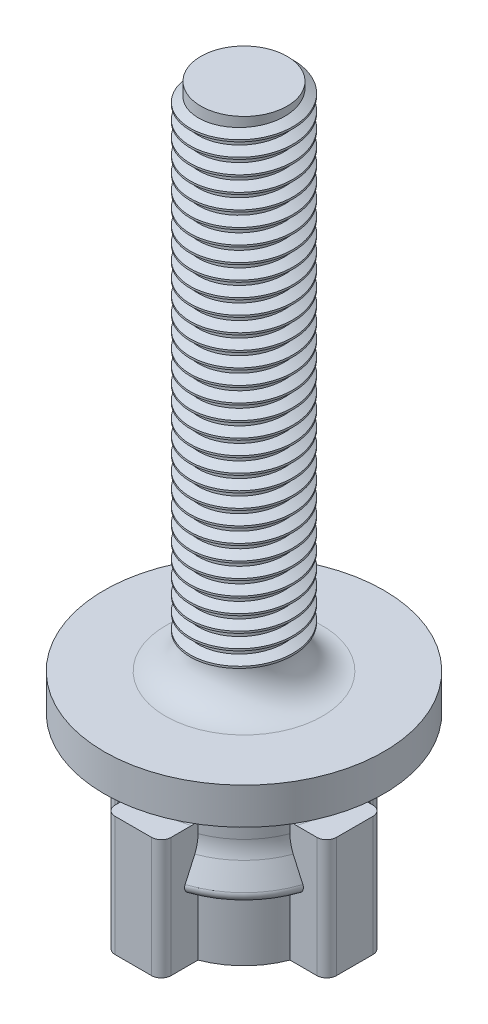
SolidWorks part; units mm, degrees
ref_plane "Alzado" through (0, 0, 0) normal (0, 0, 1) x (1, 0, 0)
ref_plane "Planta" through (0, 0, 0) normal (0, 1, 0) x (1, 0, 0)
ref_plane "Vista lateral" through (0, 0, 0) normal (1, 0, 0) x (0, 0, -1)
sketch "Croquis1" plane through (0, 0, 0) normal (0, 0, 1) x (1, 0, 0)
  line L0 (0, 0) -> (0, 10) construction
  line L1 (0, 10) -> (6.5, 10)
  line L2 (0, 0) -> (6.5, 0)
  line L3 (6.65, 0) -> (6.65, 4.8121) construction
  line L4 (6.8499, 5.007) -> (7, 5.007) construction
  line L5 (6.65, 9) -> (6.65, 10) construction
  line L6 (6.8889, 7.7374) -> (7.6384, 5.9716) construction
  line L7 (6.5, 10) -> (6.5, 9)
  line L8 (6.5, 4.8138) -> (6.5, 0)
  line L9 (6.8499, 5.157) -> (7, 5.157)
  line L10 (6.75, 7.6807) -> (7.5004, 5.9129)
  line L11 (0, 0) -> (0, 10)
  arc A0 (6.8499, 5.007) -> (6.65, 4.8121) centre (6.8499, 4.807) ccw construction
  arc A1 (7, 5.007) -> (7.6384, 5.9716) centre (7, 5.7006) ccw construction
  arc A2 (6.65, 9) -> (6.8889, 7.7374) centre (10.1063, 9) ccw construction
  arc A3 (6.8499, 5.157) -> (6.5, 4.8138) centre (6.8499, 4.807) ccw
  arc A4 (7, 5.157) -> (7.5004, 5.9129) centre (7, 5.7006) ccw
  arc A5 (6.5, 9) -> (6.75, 7.6807) centre (10.1063, 9) ccw
  dimension "D6" = 67
  dimension "D7" = 0.35
  dimension "D9" = 3.6063
  dimension "D11" = 0.15
  dimension "D1" = 10
  dimension "D2" = 6.5
  dimension "D3" = 0.15
  dimension "D4" = 4.8138
  dimension "D5" = 1
  dimension "D8" = 0.5
  dimension "D10" = 0.25
  dimension "D12" = 0.3499
  dimension "D13" = 0.35
  dimension "D15" = 0.0017
  dimension "D16" = 0.15
  dimension "D19" = 0.15
  dimension "D20" = 0.15
revolve "Revolución1" add sketch "Croquis1" angle 360 about L11
sketch "Croquis2" plane through (0, 10, 0) normal (0, 1, 0) x (1, 0, 0)
  line L0 (0, -7.5004) -> (0, 7.5004) construction
  line L1 (7.5004, 0) -> (-7.5004, 0) construction
  line L3 (-1.5, 9.3) -> (1.5, 9.3) construction
  line L4 (-2.5, 8.3) -> (-2.5, 6) construction
  line L5 (-2.5, 6) -> (2.5, 6) construction
  line L6 (2.5, 8.3) -> (2.5, 6) construction
  line L7 (-1.5, 9.1) -> (1.5, 9.1)
  line L11 (-2.3, 6.2) -> (2.3, 6.2) construction
  line L12 (2.3, 8.3) -> (2.3, 6.2) construction
  line L13 (2.3, 8.3) -> (2.3, 6)
  line L15 (-2.3, 8.3) -> (-2.3, 6.2) construction
  line L16 (-2.3, 8.3) -> (-2.3, 6)
  line L18 (-2.3, 6) -> (2.3, 6)
  line L31 (6, 2.3) -> (6, -2.3)
  line L32 (8.3, -2.3) -> (6, -2.3)
  line L33 (9.1, 1.5) -> (9.1, -1.5)
  line L34 (8.3, 2.3) -> (6, 2.3)
  line L35 (2.3, -6) -> (-2.3, -6)
  line L36 (-2.3, -8.3) -> (-2.3, -6)
  line L37 (1.5, -9.1) -> (-1.5, -9.1)
  line L38 (2.3, -8.3) -> (2.3, -6)
  line L39 (-6, -2.3) -> (-6, 2.3)
  line L40 (-8.3, 2.3) -> (-6, 2.3)
  line L41 (-9.1, -1.5) -> (-9.1, 1.5)
  line L42 (-8.3, -2.3) -> (-6, -2.3)
  arc A0 (1.5, 9.3) -> (2.5, 8.3) centre (1.5, 8.3) cw construction
  arc A1 (-1.5, 9.3) -> (-2.5, 8.3) centre (-1.5, 8.3) ccw construction
  circle A2 centre (0, 0) radius 6.5 construction
  arc A3 (1.5, 9.1) -> (2.3, 8.3) centre (1.5, 8.3) cw
  arc A4 (-1.5, 9.1) -> (-2.3, 8.3) centre (-1.5, 8.3) ccw
  circle A12 centre (0, 0) radius 7.5004 construction
  arc A13 (9.1, -1.5) -> (8.3, -2.3) centre (8.3, -1.5) cw
  arc A14 (9.1, 1.5) -> (8.3, 2.3) centre (8.3, 1.5) ccw
  arc A15 (-1.5, -9.1) -> (-2.3, -8.3) centre (-1.5, -8.3) cw
  arc A16 (1.5, -9.1) -> (2.3, -8.3) centre (1.5, -8.3) ccw
  arc A17 (-9.1, 1.5) -> (-8.3, 2.3) centre (-8.3, 1.5) cw
  arc A18 (-9.1, -1.5) -> (-8.3, -2.3) centre (-8.3, -1.5) ccw
  point P3 (0, 0)
  point P6 (0, 0)
  point P10 (0, 6)
  point P15 (-9.1, 0)
  point P16 (0, -9.1)
  point P39 (0, 0)
  point P56 (0, 0)
  dimension "D2" = 1
  dimension "D1" = 5
  dimension "D3" = 3.3
  dimension "D4" = 0.2
  dimension "D5" = 4
extrude "Saliente-Extruir1" add sketch "Croquis2" against normal up to surface (10 mm away) up to face at (0, 0, -6.5)
sketch "Croquis3" plane through (0, 10, 0) normal (0, 1, 0) x (1, 0, 0)
  line L12 (-2.3, -6.0795) -> (-2.3, -8.3)
  line L13 (2.3, 6.0795) -> (2.3, 8.3)
  line L14 (1.5, 9.1) -> (-1.5, 9.1)
  line L15 (-2.3, 8.3) -> (-2.3, 6.0795)
  line L16 (6.0795, -2.3) -> (8.3, -2.3)
  line L17 (9.1, -1.5) -> (9.1, 1.5)
  line L18 (8.3, 2.3) -> (6.0795, 2.3)
  line L19 (-2.3, -6.0795) -> (-2.3, -8.3)
  line L20 (-1.5, -9.1) -> (1.5, -9.1)
  line L21 (-1.5, -9.1) -> (1.5, -9.1)
  line L22 (2.3, -8.3) -> (2.3, -6.0795)
  line L23 (-6.0795, 2.3) -> (-8.3, 2.3)
  line L24 (-9.1, 1.5) -> (-9.1, -1.5)
  line L25 (-8.3, -2.3) -> (-6.0795, -2.3)
  line L26 (2.3, 6.0795) -> (2.3, 8.3)
  line L27 (1.5, 9.1) -> (-1.5, 9.1)
  line L28 (-2.3, 8.3) -> (-2.3, 6.0795)
  line L29 (6.0795, -2.3) -> (8.3, -2.3)
  line L30 (9.1, -1.5) -> (9.1, 1.5)
  line L31 (8.3, 2.3) -> (6.0795, 2.3)
  line L36 (-6.0795, 2.3) -> (-8.3, 2.3)
  line L37 (-9.1, 1.5) -> (-9.1, -1.5)
  line L38 (-8.3, -2.3) -> (-6.0795, -2.3)
  line L39 (2.3, -8.3) -> (2.3, -6.0795)
  arc A12 (-6.0795, -2.3) -> (-2.3, -6.0795) centre (0, 0) ccw
  arc A13 (2.3, 8.3) -> (1.5, 9.1) centre (1.5, 8.3) ccw
  arc A14 (-1.5, 9.1) -> (-2.3, 8.3) centre (-1.5, 8.3) ccw
  arc A15 (-2.3, 6.0795) -> (-6.0795, 2.3) centre (0, 0) ccw
  arc A16 (8.3, -2.3) -> (9.1, -1.5) centre (8.3, -1.5) ccw
  arc A17 (9.1, 1.5) -> (8.3, 2.3) centre (8.3, 1.5) ccw
  arc A18 (6.0795, 2.3) -> (2.3, 6.0795) centre (0, 0) ccw
  arc A19 (-2.3, -8.3) -> (-1.5, -9.1) centre (-1.5, -8.3) ccw
  arc A20 (-2.3, -8.3) -> (-1.5, -9.1) centre (-1.5, -8.3) ccw
  arc A21 (1.5, -9.1) -> (2.3, -8.3) centre (1.5, -8.3) ccw
  arc A22 (-8.3, 2.3) -> (-9.1, 1.5) centre (-8.3, 1.5) ccw
  arc A23 (-9.1, -1.5) -> (-8.3, -2.3) centre (-8.3, -1.5) ccw
  arc A24 (-6.0795, -2.3) -> (-2.3, -6.0795) centre (0, 0) ccw
  arc A25 (2.3, 8.3) -> (1.5, 9.1) centre (1.5, 8.3) ccw
  arc A26 (-1.5, 9.1) -> (-2.3, 8.3) centre (-1.5, 8.3) ccw
  arc A27 (-2.3, 6.0795) -> (-6.0795, 2.3) centre (0, 0) ccw
  arc A28 (8.3, -2.3) -> (9.1, -1.5) centre (8.3, -1.5) ccw
  arc A29 (9.1, 1.5) -> (8.3, 2.3) centre (8.3, 1.5) ccw
  arc A30 (6.0795, 2.3) -> (2.3, 6.0795) centre (0, 0) ccw
  arc A34 (-8.3, 2.3) -> (-9.1, 1.5) centre (-8.3, 1.5) ccw
  arc A35 (-9.1, -1.5) -> (-8.3, -2.3) centre (-8.3, -1.5) ccw
  arc A36 (1.5, -9.1) -> (2.3, -8.3) centre (1.5, -8.3) ccw
  arc A37 (2.3, -6.0795) -> (6.0795, -2.3) centre (0, 0) ccw
  arc A38 (2.3, -6.0795) -> (6.0795, -2.3) centre (0, 0) ccw
  dimension "D1" = 0
extrude "Cortar-Extruir1" cut sketch "Croquis3" against normal blind 0.15
sketch "Croquis5" plane through (0, 9.85, 0) normal (0, 1, 0) x (1, 0, 0)
  circle A1 centre (0, 0) radius 6
  dimension "D1" = 12
extrude "Saliente-Extruir2" add sketch "Croquis5" along normal blind 3.55
sketch "Croquis6" plane through (0, 13.4, 0) normal (0, 1, 0) x (1, 0, 0)
  circle A0 centre (0, 0) radius 11.5
  dimension "D1" = 23
extrude "Saliente-Extruir3" add sketch "Croquis6" along normal blind 3
sketch "Croquis8" plane through (0, 16.4, 0) normal (0, 1, 0) x (1, 0, 0)
  circle A0 centre (0, 0) radius 3.55
  dimension "D1" = 7.1
extrude "Saliente-Extruir4" add sketch "Croquis8" along normal blind 42
fillet "Redondeo5" radius 1 2 edges at (0, 9.85, 6) (0, 13.4, 6)
thread "Rosca1" pitch 1.25 profile "Perfil de rosca1" start angle 0, offset 0, length 39, pitch 1.25, diameter 7.1
ref_plane "Plano1" through (-3.55, 58.4, 0) normal (0, 0, 1) x (-1, 0, 0)
sketch "Perfil de rosca1" plane through (-3.55, 58.4, 0) normal (0, 0, 1) x (-1, 0, 0)
  line L0 (0, 0) -> (0, 1.25) construction
  line L1 (0, 0) -> (0.6766, 0.3906)
  line L2 (0.6766, 0.3906) -> (0.6766, 0.5469)
  line L3 (0.6766, 0.5469) -> (0, 0.9375)
  line L4 (0.6766, 0.4687) -> (0, 0.4687) construction
  line L11 (0, 0) -> (0, 0.9375)
  point P2 (0, 0)
  dimension "Pitch" = 1.25
  dimension "Profile_Angle" = 60
  dimension "Profile_Land" = 0.1562
  dimension "Profile_Height" = 0.6766
sketch3d "Croquis3D1"
  spline S0 degree 2 poles (-4.2266, 57.8531, 0) (-4.2266, 57.775, -1.7507) (-2.9886, 57.6969, -2.9886) (-1.7507, 57.6188, -4.2266) (0, 57.5406, -4.2266) (1.7507, 57.4625, -4.2266) (2.9886, 57.3844, -2.9886) (4.2266, 57.3063, -1.7507) (4.2266, 57.2281, 0) (4.2266, 57.15, 1.7507) (2.9886, 57.0719, 2.9886) (1.7507, 56.9938, 4.2266) (0, 56.9156, 4.2266) (-1.7507, 56.8375, 4.2266) (-2.9886, 56.7594, 2.9886) (-4.2266, 56.6813, 1.7507) (-4.2266, 56.6031, 0) (-4.2266, 56.525, -1.7507) (-2.9886, 56.4469, -2.9886) (-1.7507, 56.3688, -4.2266) (0, 56.2906, -4.2266) (1.7507, 56.2125, -4.2266) (2.9886, 56.1344, -2.9886) (4.2266, 56.0563, -1.7507) (4.2266, 55.9781, 0) (4.2266, 55.9, 1.7507) (2.9886, 55.8219, 2.9886) (1.7507, 55.7438, 4.2266) (0, 55.6656, 4.2266) (-1.7507, 55.5875, 4.2266) (-2.9886, 55.5094, 2.9886) (-4.2266, 55.4313, 1.7507) (-4.2266, 55.3531, 0) (-4.2266, 55.275, -1.7507) (-2.9886, 55.1969, -2.9886) (-1.7507, 55.1188, -4.2266) (0, 55.0406, -4.2266) (1.7507, 54.9625, -4.2266) (2.9886, 54.8844, -2.9886) (4.2266, 54.8063, -1.7507) (4.2266, 54.7281, 0) (4.2266, 54.65, 1.7507) (2.9886, 54.5719, 2.9886) (1.7507, 54.4938, 4.2266) (0, 54.4156, 4.2266) (-1.7507, 54.3375, 4.2266) (-2.9886, 54.2594, 2.9886) (-4.2266, 54.1813, 1.7507) (-4.2266, 54.1031, 0) (-4.2266, 54.025, -1.7507) (-2.9886, 53.9469, -2.9886) (-1.7507, 53.8688, -4.2266) (0, 53.7906, -4.2266) (1.7507, 53.7125, -4.2266) (2.9886, 53.6344, -2.9886) (4.2266, 53.5563, -1.7507) (4.2266, 53.4781, 0) (4.2266, 53.4, 1.7507) (2.9886, 53.3219, 2.9886) (1.7507, 53.2438, 4.2266) (0, 53.1656, 4.2266) (-1.7507, 53.0875, 4.2266) (-2.9886, 53.0094, 2.9886) (-4.2266, 52.9313, 1.7507) (-4.2266, 52.8531, 0) (-4.2266, 52.775, -1.7507) (-2.9886, 52.6969, -2.9886) (-1.7507, 52.6188, -4.2266) (0, 52.5406, -4.2266) (1.7507, 52.4625, -4.2266) (2.9886, 52.3844, -2.9886) (4.2266, 52.3063, -1.7507) (4.2266, 52.2281, 0) (4.2266, 52.15, 1.7507) (2.9886, 52.0719, 2.9886) (1.7507, 51.9938, 4.2266) (0, 51.9156, 4.2266) (-1.7507, 51.8375, 4.2266) (-2.9886, 51.7594, 2.9886) (-4.2266, 51.6813, 1.7507) (-4.2266, 51.6031, 0) (-4.2266, 51.525, -1.7507) (-2.9886, 51.4469, -2.9886) (-1.7507, 51.3688, -4.2266) (0, 51.2906, -4.2266) (1.7507, 51.2125, -4.2266) (2.9886, 51.1344, -2.9886) (4.2266, 51.0563, -1.7507) (4.2266, 50.9781, 0) (4.2266, 50.9, 1.7507) (2.9886, 50.8219, 2.9886) (1.7507, 50.7438, 4.2266) (0, 50.6656, 4.2266) (-1.7507, 50.5875, 4.2266) (-2.9886, 50.5094, 2.9886) (-4.2266, 50.4313, 1.7507) (-4.2266, 50.3531, 0) (-4.2266, 50.275, -1.7507) (-2.9886, 50.1969, -2.9886) (-1.7507, 50.1188, -4.2266) (0, 50.0406, -4.2266) (1.7507, 49.9625, -4.2266) (2.9886, 49.8844, -2.9886) (4.2266, 49.8063, -1.7507) (4.2266, 49.7281, 0) (4.2266, 49.65, 1.7507) (2.9886, 49.5719, 2.9886) (1.7507, 49.4938, 4.2266) (0, 49.4156, 4.2266) (-1.7507, 49.3375, 4.2266) (-2.9886, 49.2594, 2.9886) (-4.2266, 49.1813, 1.7507) (-4.2266, 49.1031, 0) (-4.2266, 49.025, -1.7507) (-2.9886, 48.9469, -2.9886) (-1.7507, 48.8688, -4.2266) (0, 48.7906, -4.2266) (1.7507, 48.7125, -4.2266) (2.9886, 48.6344, -2.9886) (4.2266, 48.5563, -1.7507) (4.2266, 48.4781, 0) (4.2266, 48.4, 1.7507) (2.9886, 48.3219, 2.9886) (1.7507, 48.2438, 4.2266) (0, 48.1656, 4.2266) (-1.7507, 48.0875, 4.2266) (-2.9886, 48.0094, 2.9886) (-4.2266, 47.9313, 1.7507) (-4.2266, 47.8531, 0) (-4.2266, 47.775, -1.7507) (-2.9886, 47.6969, -2.9886) (-1.7507, 47.6188, -4.2266) (0, 47.5406, -4.2266) (1.7507, 47.4625, -4.2266) (2.9886, 47.3844, -2.9886) (4.2266, 47.3063, -1.7507) (4.2266, 47.2281, 0) (4.2266, 47.15, 1.7507) (2.9886, 47.0719, 2.9886) (1.7507, 46.9938, 4.2266) (0, 46.9156, 4.2266) (-1.7507, 46.8375, 4.2266) (-2.9886, 46.7594, 2.9886) (-4.2266, 46.6813, 1.7507) (-4.2266, 46.6031, 0) (-4.2266, 46.525, -1.7507) (-2.9886, 46.4469, -2.9886) (-1.7507, 46.3688, -4.2266) (0, 46.2906, -4.2266) (1.7507, 46.2125, -4.2266) (2.9886, 46.1344, -2.9886) (4.2266, 46.0563, -1.7507) (4.2266, 45.9781, 0) (4.2266, 45.9, 1.7507) (2.9886, 45.8219, 2.9886) (1.7507, 45.7438, 4.2266) (0, 45.6656, 4.2266) (-1.7507, 45.5875, 4.2266) (-2.9886, 45.5094, 2.9886) (-4.2266, 45.4313, 1.7507) (-4.2266, 45.3531, 0) (-4.2266, 45.275, -1.7507) (-2.9886, 45.1969, -2.9886) (-1.7507, 45.1188, -4.2266) (0, 45.0406, -4.2266) (1.7507, 44.9625, -4.2266) (2.9886, 44.8844, -2.9886) (4.2266, 44.8063, -1.7507) (4.2266, 44.7281, 0) (4.2266, 44.65, 1.7507) (2.9886, 44.5719, 2.9886) (1.7507, 44.4938, 4.2266) (0, 44.4156, 4.2266) (-1.7507, 44.3375, 4.2266) (-2.9886, 44.2594, 2.9886) (-4.2266, 44.1813, 1.7507) (-4.2266, 44.1031, 0) (-4.2266, 44.025, -1.7507) (-2.9886, 43.9469, -2.9886) (-1.7507, 43.8688, -4.2266) (0, 43.7906, -4.2266) (1.7507, 43.7125, -4.2266) (2.9886, 43.6344, -2.9886) (4.2266, 43.5563, -1.7507) (4.2266, 43.4781, 0) (4.2266, 43.4, 1.7507) (2.9886, 43.3219, 2.9886) (1.7507, 43.2438, 4.2266) (0, 43.1656, 4.2266) (-1.7507, 43.0875, 4.2266) (-2.9886, 43.0094, 2.9886) (-4.2266, 42.9313, 1.7507) (-4.2266, 42.8531, 0) (-4.2266, 42.775, -1.7507) (-2.9886, 42.6969, -2.9886) (-1.7507, 42.6188, -4.2266) (0, 42.5406, -4.2266) (1.7507, 42.4625, -4.2266) (2.9886, 42.3844, -2.9886) (4.2266, 42.3063, -1.7507) (4.2266, 42.2281, 0) (4.2266, 42.15, 1.7507) (2.9886, 42.0719, 2.9886) (1.7507, 41.9938, 4.2266) (0, 41.9156, 4.2266) (-1.7507, 41.8375, 4.2266) (-2.9886, 41.7594, 2.9886) (-4.2266, 41.6813, 1.7507) (-4.2266, 41.6031, 0) (-4.2266, 41.525, -1.7507) (-2.9886, 41.4469, -2.9886) (-1.7507, 41.3688, -4.2266) (0, 41.2906, -4.2266) (1.7507, 41.2125, -4.2266) (2.9886, 41.1344, -2.9886) (4.2266, 41.0563, -1.7507) (4.2266, 40.9781, 0) (4.2266, 40.9, 1.7507) (2.9886, 40.8219, 2.9886) (1.7507, 40.7438, 4.2266) (0, 40.6656, 4.2266) (-1.7507, 40.5875, 4.2266) (-2.9886, 40.5094, 2.9886) (-4.2266, 40.4313, 1.7507) (-4.2266, 40.3531, 0) (-4.2266, 40.275, -1.7507) (-2.9886, 40.1969, -2.9886) (-1.7507, 40.1188, -4.2266) (0, 40.0406, -4.2266) (1.7507, 39.9625, -4.2266) (2.9886, 39.8844, -2.9886) (4.2266, 39.8063, -1.7507) (4.2266, 39.7281, 0) (4.2266, 39.65, 1.7507) (2.9886, 39.5719, 2.9886) (1.7507, 39.4938, 4.2266) (0, 39.4156, 4.2266) (-1.7507, 39.3375, 4.2266) (-2.9886, 39.2594, 2.9886) (-4.2266, 39.1813, 1.7507) (-4.2266, 39.1031, 0) (-4.2266, 39.025, -1.7507) (-2.9886, 38.9469, -2.9886) (-1.7507, 38.8688, -4.2266) (0, 38.7906, -4.2266) (1.7507, 38.7125, -4.2266) (2.9886, 38.6344, -2.9886) (4.2266, 38.5563, -1.7507) (4.2266, 38.4781, 0) (4.2266, 38.4, 1.7507) (2.9886, 38.3219, 2.9886) (1.7507, 38.2438, 4.2266) (0, 38.1656, 4.2266) (-1.7507, 38.0875, 4.2266) (-2.9886, 38.0094, 2.9886) (-4.2266, 37.9313, 1.7507) (-4.2266, 37.8531, 0) (-4.2266, 37.775, -1.7507) (-2.9886, 37.6969, -2.9886) (-1.7507, 37.6188, -4.2266) (0, 37.5406, -4.2266) (1.7507, 37.4625, -4.2266) (2.9886, 37.3844, -2.9886) (4.2266, 37.3063, -1.7507) (4.2266, 37.2281, 0) (4.2266, 37.15, 1.7507) (2.9886, 37.0719, 2.9886) (1.7507, 36.9938, 4.2266) (0, 36.9156, 4.2266) (-1.7507, 36.8375, 4.2266) (-2.9886, 36.7594, 2.9886) (-4.2266, 36.6813, 1.7507) (-4.2266, 36.6031, 0) (-4.2266, 36.525, -1.7507) (-2.9886, 36.4469, -2.9886) (-1.7507, 36.3688, -4.2266) (0, 36.2906, -4.2266) (1.7507, 36.2125, -4.2266) (2.9886, 36.1344, -2.9886) (4.2266, 36.0563, -1.7507) (4.2266, 35.9781, 0) (4.2266, 35.9, 1.7507) (2.9886, 35.8219, 2.9886) (1.7507, 35.7438, 4.2266) (0, 35.6656, 4.2266) (-1.7507, 35.5875, 4.2266) (-2.9886, 35.5094, 2.9886) (-4.2266, 35.4313, 1.7507) (-4.2266, 35.3531, 0) (-4.2266, 35.275, -1.7507) (-2.9886, 35.1969, -2.9886) (-1.7507, 35.1188, -4.2266) (0, 35.0406, -4.2266) (1.7507, 34.9625, -4.2266) (2.9886, 34.8844, -2.9886) (4.2266, 34.8063, -1.7507) (4.2266, 34.7281, 0) (4.2266, 34.65, 1.7507) (2.9886, 34.5719, 2.9886) (1.7507, 34.4938, 4.2266) (0, 34.4156, 4.2266) (-1.7507, 34.3375, 4.2266) (-2.9886, 34.2594, 2.9886) (-4.2266, 34.1813, 1.7507) (-4.2266, 34.1031, 0) (-4.2266, 34.025, -1.7507) (-2.9886, 33.9469, -2.9886) (-1.7507, 33.8688, -4.2266) (0, 33.7906, -4.2266) (1.7507, 33.7125, -4.2266) (2.9886, 33.6344, -2.9886) (4.2266, 33.5563, -1.7507) (4.2266, 33.4781, 0) (4.2266, 33.4, 1.7507) (2.9886, 33.3219, 2.9886) (1.7507, 33.2438, 4.2266) (0, 33.1656, 4.2266) (-1.7507, 33.0875, 4.2266) (-2.9886, 33.0094, 2.9886) (-4.2266, 32.9313, 1.7507) (-4.2266, 32.8531, 0) (-4.2266, 32.775, -1.7507) (-2.9886, 32.6969, -2.9886) (-1.7507, 32.6188, -4.2266) (0, 32.5406, -4.2266) (1.7507, 32.4625, -4.2266) (2.9886, 32.3844, -2.9886) (4.2266, 32.3063, -1.7507) (4.2266, 32.2281, 0) (4.2266, 32.15, 1.7507) (2.9886, 32.0719, 2.9886) (1.7507, 31.9938, 4.2266) (0, 31.9156, 4.2266) (-1.7507, 31.8375, 4.2266) (-2.9886, 31.7594, 2.9886) (-4.2266, 31.6813, 1.7507) (-4.2266, 31.6031, 0) (-4.2266, 31.525, -1.7507) (-2.9886, 31.4469, -2.9886) (-1.7507, 31.3688, -4.2266) (0, 31.2906, -4.2266) (1.7507, 31.2125, -4.2266) (2.9886, 31.1344, -2.9886) (4.2266, 31.0563, -1.7507) (4.2266, 30.9781, 0) (4.2266, 30.9, 1.7507) (2.9886, 30.8219, 2.9886) (1.7507, 30.7438, 4.2266) (0, 30.6656, 4.2266) (-1.7507, 30.5875, 4.2266) (-2.9886, 30.5094, 2.9886) (-4.2266, 30.4313, 1.7507) (-4.2266, 30.3531, 0) (-4.2266, 30.275, -1.7507) (-2.9886, 30.1969, -2.9886) (-1.7507, 30.1188, -4.2266) (0, 30.0406, -4.2266) (1.7507, 29.9625, -4.2266) (2.9886, 29.8844, -2.9886) (4.2266, 29.8063, -1.7507) (4.2266, 29.7281, 0) (4.2266, 29.65, 1.7507) (2.9886, 29.5719, 2.9886) (1.7507, 29.4938, 4.2266) (0, 29.4156, 4.2266) (-1.7507, 29.3375, 4.2266) (-2.9886, 29.2594, 2.9886) (-4.2266, 29.1813, 1.7507) (-4.2266, 29.1031, 0) (-4.2266, 29.025, -1.7507) (-2.9886, 28.9469, -2.9886) (-1.7507, 28.8688, -4.2266) (0, 28.7906, -4.2266) (1.7507, 28.7125, -4.2266) (2.9886, 28.6344, -2.9886) (4.2266, 28.5563, -1.7507) (4.2266, 28.4781, 0) (4.2266, 28.4, 1.7507) (2.9886, 28.3219, 2.9886) (1.7507, 28.2438, 4.2266) (0, 28.1656, 4.2266) (-1.7507, 28.0875, 4.2266) (-2.9886, 28.0094, 2.9886) (-4.2266, 27.9313, 1.7507) (-4.2266, 27.8531, 0) (-4.2266, 27.775, -1.7507) (-2.9886, 27.6969, -2.9886) (-1.7507, 27.6188, -4.2266) (0, 27.5406, -4.2266) (1.7507, 27.4625, -4.2266) (2.9886, 27.3844, -2.9886) (4.2266, 27.3063, -1.7507) (4.2266, 27.2281, 0) (4.2266, 27.15, 1.7507) (2.9886, 27.0719, 2.9886) (1.7507, 26.9938, 4.2266) (0, 26.9156, 4.2266) (-1.7507, 26.8375, 4.2266) (-2.9886, 26.7594, 2.9886) (-4.2266, 26.6813, 1.7507) (-4.2266, 26.6031, 0) (-4.2266, 26.525, -1.7507) (-2.9886, 26.4469, -2.9886) (-1.7507, 26.3688, -4.2266) (0, 26.2906, -4.2266) (1.7507, 26.2125, -4.2266) (2.9886, 26.1344, -2.9886) (4.2266, 26.0563, -1.7507) (4.2266, 25.9781, 0) (4.2266, 25.9, 1.7507) (2.9886, 25.8219, 2.9886) (1.7507, 25.7438, 4.2266) (0, 25.6656, 4.2266) (-1.7507, 25.5875, 4.2266) (-2.9886, 25.5094, 2.9886) (-4.2266, 25.4313, 1.7507) (-4.2266, 25.3531, 0) (-4.2266, 25.275, -1.7507) (-2.9886, 25.1969, -2.9886) (-1.7507, 25.1188, -4.2266) (0, 25.0406, -4.2266) (1.7507, 24.9625, -4.2266) (2.9886, 24.8844, -2.9886) (4.2266, 24.8063, -1.7507) (4.2266, 24.7281, 0) (4.2266, 24.65, 1.7507) (2.9886, 24.5719, 2.9886) (1.7507, 24.4938, 4.2266) (0, 24.4156, 4.2266) (-1.7507, 24.3375, 4.2266) (-2.9886, 24.2594, 2.9886) (-4.2266, 24.1813, 1.7507) (-4.2266, 24.1031, 0) (-4.2266, 24.025, -1.7507) (-2.9886, 23.9469, -2.9886) (-1.7507, 23.8688, -4.2266) (0, 23.7906, -4.2266) (1.7507, 23.7125, -4.2266) (2.9886, 23.6344, -2.9886) (4.2266, 23.5563, -1.7507) (4.2266, 23.4781, 0) (4.2266, 23.4, 1.7507) (2.9886, 23.3219, 2.9886) (1.7507, 23.2438, 4.2266) (0, 23.1656, 4.2266) (-1.7507, 23.0875, 4.2266) (-2.9886, 23.0094, 2.9886) (-4.2266, 22.9313, 1.7507) (-4.2266, 22.8531, 0) (-4.2266, 22.775, -1.7507) (-2.9886, 22.6969, -2.9886) (-1.7507, 22.6188, -4.2266) (0, 22.5406, -4.2266) (1.7507, 22.4625, -4.2266) (2.9886, 22.3844, -2.9886) (4.2266, 22.3063, -1.7507) (4.2266, 22.2281, 0) (4.2266, 22.15, 1.7507) (2.9886, 22.0719, 2.9886) (1.7507, 21.9938, 4.2266) (0, 21.9156, 4.2266) (-1.7507, 21.8375, 4.2266) (-2.9886, 21.7594, 2.9886) (-4.2266, 21.6813, 1.7507) (-4.2266, 21.6031, 0) (-4.2266, 21.525, -1.7507) (-2.9886, 21.4469, -2.9886) (-1.7507, 21.3688, -4.2266) (0, 21.2906, -4.2266) (1.7507, 21.2125, -4.2266) (2.9886, 21.1344, -2.9886) (4.2266, 21.0563, -1.7507) (4.2266, 20.9781, 0) (4.2266, 20.9, 1.7507) (2.9886, 20.8219, 2.9886) (1.7507, 20.7438, 4.2266) (0, 20.6656, 4.2266) (-1.7507, 20.5875, 4.2266) (-2.9886, 20.5094, 2.9886) (-4.2266, 20.4313, 1.7507) (-4.2266, 20.3531, 0) (-4.2266, 20.275, -1.7507) (-2.9886, 20.1969, -2.9886) (-1.7507, 20.1188, -4.2266) (0, 20.0406, -4.2266) (1.7507, 19.9625, -4.2266) (2.9886, 19.8844, -2.9886) (4.2266, 19.8063, -1.7507) (4.2266, 19.7281, 0) (4.2266, 19.65, 1.7507) (2.9886, 19.5719, 2.9886) (1.7507, 19.4938, 4.2266) (0, 19.4156, 4.2266) (-1.7507, 19.3375, 4.2266) (-2.9886, 19.2594, 2.9886) (-4.2266, 19.1813, 1.7507) (-4.2266, 19.1031, 0) (-4.2266, 19.025, -1.7507) (-2.9886, 18.9469, -2.9886) (-2.2711, 18.9016, -3.7061) (-1.3061, 18.8527, -4.0197) knots 0 0 0 0.003906 0.003906 0.007812 0.007812 0.011719 0.011719 0.015625 0.015625 0.019531 0.019531 0.023438 0.023438 0.027344 0.027344 0.03125 0.03125 0.035156 0.035156 0.039062 0.039062 0.042969 0.042969 0.046875 0.046875 0.050781 0.050781 0.054688 0.054688 0.058594 0.058594 0.0625 0.0625 0.066406 0.066406 0.070312 0.070312 0.074219 0.074219 0.078125 0.078125 0.082031 0.082031 0.085938 0.085938 0.089844 0.089844 0.09375 0.09375 0.097656 0.097656 0.101562 0.101562 0.105469 0.105469 0.109375 0.109375 0.113281 0.113281 0.117188 0.117188 0.121094 0.121094 0.125 0.125 0.128906 0.128906 0.132812 0.132812 0.136719 0.136719 0.140625 0.140625 0.144531 0.144531 0.148438 0.148438 0.152344 0.152344 0.15625 0.15625 0.160156 0.160156 0.164062 0.164062 0.167969 0.167969 0.171875 0.171875 0.175781 0.175781 0.179688 0.179688 0.183594 0.183594 0.1875 0.1875 0.191406 0.191406 0.195312 0.195312 0.199219 0.199219 0.203125 0.203125 0.207031 0.207031 0.210938 0.210938 0.214844 0.214844 0.21875 0.21875 0.222656 0.222656 0.226562 0.226562 0.230469 0.230469 0.234375 0.234375 0.238281 0.238281 0.242188 0.242188 0.246094 0.246094 0.25 0.25 0.253906 0.253906 0.257812 0.257812 0.261719 0.261719 0.265625 0.265625 0.269531 0.269531 0.273438 0.273438 0.277344 0.277344 0.28125 0.28125 0.285156 0.285156 0.289062 0.289062 0.292969 0.292969 0.296875 0.296875 0.300781 0.300781 0.304688 0.304688 0.308594 0.308594 0.3125 0.3125 0.316406 0.316406 0.320312 0.320312 0.324219 0.324219 0.328125 0.328125 0.332031 0.332031 0.335938 0.335938 0.339844 0.339844 0.34375 0.34375 0.347656 0.347656 0.351562 0.351562 0.355469 0.355469 0.359375 0.359375 0.363281 0.363281 0.367188 0.367188 0.371094 0.371094 0.375 0.375 0.378906 0.378906 0.382812 0.382812 0.386719 0.386719 0.390625 0.390625 0.394531 0.394531 0.398438 0.398438 0.402344 0.402344 0.40625 0.40625 0.410156 0.410156 0.414062 0.414062 0.417969 0.417969 0.421875 0.421875 0.425781 0.425781 0.429688 0.429688 0.433594 0.433594 0.4375 0.4375 0.441406 0.441406 0.445312 0.445312 0.449219 0.449219 0.453125 0.453125 0.457031 0.457031 0.460938 0.460938 0.464844 0.464844 0.46875 0.46875 0.472656 0.472656 0.476562 0.476562 0.480469 0.480469 0.484375 0.484375 0.488281 0.488281 0.492188 0.492188 0.496094 0.496094 0.5 0.5 0.503906 0.503906 0.507812 0.507812 0.511719 0.511719 0.515625 0.515625 0.519531 0.519531 0.523438 0.523438 0.527344 0.527344 0.53125 0.53125 0.535156 0.535156 0.539062 0.539062 0.542969 0.542969 0.546875 0.546875 0.550781 0.550781 0.554688 0.554688 0.558594 0.558594 0.5625 0.5625 0.566406 0.566406 0.570312 0.570312 0.574219 0.574219 0.578125 0.578125 0.582031 0.582031 0.585938 0.585938 0.589844 0.589844 0.59375 0.59375 0.597656 0.597656 0.601562 0.601562 0.605469 0.605469 0.609375 0.609375 0.613281 0.613281 0.617188 0.617188 0.621094 0.621094 0.625 0.625 0.628906 0.628906 0.632812 0.632812 0.636719 0.636719 0.640625 0.640625 0.644531 0.644531 0.648438 0.648438 0.652344 0.652344 0.65625 0.65625 0.660156 0.660156 0.664062 0.664062 0.667969 0.667969 0.671875 0.671875 0.675781 0.675781 0.679688 0.679688 0.683594 0.683594 0.6875 0.6875 0.691406 0.691406 0.695312 0.695312 0.699219 0.699219 0.703125 0.703125 0.707031 0.707031 0.710938 0.710938 0.714844 0.714844 0.71875 0.71875 0.722656 0.722656 0.726562 0.726562 0.730469 0.730469 0.734375 0.734375 0.738281 0.738281 0.742188 0.742188 0.746094 0.746094 0.75 0.75 0.753906 0.753906 0.757812 0.757812 0.761719 0.761719 0.765625 0.765625 0.769531 0.769531 0.773438 0.773438 0.777344 0.777344 0.78125 0.78125 0.785156 0.785156 0.789062 0.789062 0.792969 0.792969 0.796875 0.796875 0.800781 0.800781 0.804688 0.804688 0.808594 0.808594 0.8125 0.8125 0.816406 0.816406 0.820312 0.820312 0.824219 0.824219 0.828125 0.828125 0.832031 0.832031 0.835938 0.835938 0.839844 0.839844 0.84375 0.84375 0.847656 0.847656 0.851562 0.851562 0.855469 0.855469 0.859375 0.859375 0.863281 0.863281 0.867188 0.867188 0.871094 0.871094 0.875 0.875 0.878906 0.878906 0.882812 0.882812 0.886719 0.886719 0.890625 0.890625 0.894531 0.894531 0.898438 0.898438 0.902344 0.902344 0.90625 0.90625 0.910156 0.910156 0.914062 0.914062 0.917969 0.917969 0.921875 0.921875 0.925781 0.925781 0.929688 0.929688 0.933594 0.933594 0.9375 0.9375 0.941406 0.941406 0.945312 0.945312 0.949219 0.949219 0.953125 0.953125 0.957031 0.957031 0.960938 0.960938 0.964844 0.964844 0.96875 0.96875 0.972656 0.972656 0.974995 0.974995 0.974995 weights 1 0.92388 1 0.92388 1 0.92388 1 0.92388 1 0.92388 1 0.92388 1 0.92388 1 0.92388 1 0.92388 1 0.92388 1 0.92388 1 0.92388 1 0.92388 1 0.92388 1 0.92388 1 0.92388 1 0.92388 1 0.92388 1 0.92388 1 0.92388 1 0.92388 1 0.92388 1 0.92388 1 0.92388 1 0.92388 1 0.92388 1 0.92388 1 0.92388 1 0.92388 1 0.92388 1 0.92388 1 0.92388 1 0.92388 1 0.92388 1 0.92388 1 0.92388 1 0.92388 1 0.92388 1 0.92388 1 0.92388 1 0.92388 1 0.92388 1 0.92388 1 0.92388 1 0.92388 1 0.92388 1 0.92388 1 0.92388 1 0.92388 1 0.92388 1 0.92388 1 0.92388 1 0.92388 1 0.92388 1 0.92388 1 0.92388 1 0.92388 1 0.92388 1 0.92388 1 0.92388 1 0.92388 1 0.92388 1 0.92388 1 0.92388 1 0.92388 1 0.92388 1 0.92388 1 0.92388 1 0.92388 1 0.92388 1 0.92388 1 0.92388 1 0.92388 1 0.92388 1 0.92388 1 0.92388 1 0.92388 1 0.92388 1 0.92388 1 0.92388 1 0.92388 1 0.92388 1 0.92388 1 0.92388 1 0.92388 1 0.92388 1 0.92388 1 0.92388 1 0.92388 1 0.92388 1 0.92388 1 0.92388 1 0.92388 1 0.92388 1 0.92388 1 0.92388 1 0.92388 1 0.92388 1 0.92388 1 0.92388 1 0.92388 1 0.92388 1 0.92388 1 0.92388 1 0.92388 1 0.92388 1 0.92388 1 0.92388 1 0.92388 1 0.92388 1 0.92388 1 0.92388 1 0.92388 1 0.92388 1 0.92388 1 0.92388 1 0.92388 1 0.92388 1 0.92388 1 0.92388 1 0.92388 1 0.92388 1 0.92388 1 0.92388 1 0.92388 1 0.92388 1 0.92388 1 0.92388 1 0.92388 1 0.92388 1 0.92388 1 0.92388 1 0.92388 1 0.92388 1 0.92388 1 0.92388 1 0.92388 1 0.92388 1 0.92388 1 0.92388 1 0.92388 1 0.92388 1 0.92388 1 0.92388 1 0.92388 1 0.92388 1 0.92388 1 0.92388 1 0.92388 1 0.92388 1 0.92388 1 0.92388 1 0.92388 1 0.92388 1 0.92388 1 0.92388 1 0.92388 1 0.92388 1 0.92388 1 0.92388 1 0.92388 1 0.92388 1 0.92388 1 0.92388 1 0.92388 1 0.92388 1 0.92388 1 0.92388 1 0.92388 1 0.92388 1 0.92388 1 0.92388 1 0.92388 1 0.92388 1 0.92388 1 0.92388 1 0.92388 1 0.92388 1 0.92388 1 0.92388 1 0.92388 1 0.92388 1 0.92388 1 0.92388 1 0.92388 1 0.92388 1 0.92388 1 0.92388 1 0.92388 1 0.92388 1 0.92388 1 0.92388 1 0.92388 1 0.92388 1 0.92388 1 0.92388 1 0.92388 1 0.92388 1 0.92388 1 0.92388 1 0.92388 1 0.92388 1 0.92388 1 0.92388 1 0.92388 1 0.92388 1 0.92388 1 0.92388 1 0.92388 1 0.92388 1 0.92388 1 0.92388 1 0.92388 1 0.92388 1 0.92388 1 0.92388 1 0.92388 1 0.92388 1 0.92388 1 0.92388 1 0.92388 1 0.92388 1 0.92388 1 0.92388 1 0.92388 1 0.92388 1 0.92388 1 0.92388 1 0.92388 1 0.92388 1 0.92388 1 0.92388 1 0.92388 1 0.92388 1 0.92388 1 0.92388 1 0.92388 1 0.92388 1 0.92388 1 0.92388 1 0.92388 1 0.92388 1 0.92388 1 0.92388 1 0.92388 1 0.92388 1 0.92388 1 0.92388 1 0.92388 1 0.954422 0.963425 construction
  spline S1 degree 2 poles (-4.2266, 57.8531, 0) (-4.2266, 57.775, -1.7507) (-2.9886, 57.6969, -2.9886) (-1.7507, 57.6188, -4.2266) (0, 57.5406, -4.2266) (1.7507, 57.4625, -4.2266) (2.9886, 57.3844, -2.9886) (4.2266, 57.3063, -1.7507) (4.2266, 57.2281, 0) (4.2266, 57.15, 1.7507) (2.9886, 57.0719, 2.9886) (1.7507, 56.9938, 4.2266) (0, 56.9156, 4.2266) (-1.7507, 56.8375, 4.2266) (-2.9886, 56.7594, 2.9886) (-4.2266, 56.6813, 1.7507) (-4.2266, 56.6031, 0) (-4.2266, 56.525, -1.7507) (-2.9886, 56.4469, -2.9886) (-1.7507, 56.3688, -4.2266) (0, 56.2906, -4.2266) (1.7507, 56.2125, -4.2266) (2.9886, 56.1344, -2.9886) (4.2266, 56.0563, -1.7507) (4.2266, 55.9781, 0) (4.2266, 55.9, 1.7507) (2.9886, 55.8219, 2.9886) (1.7507, 55.7438, 4.2266) (0, 55.6656, 4.2266) (-1.7507, 55.5875, 4.2266) (-2.9886, 55.5094, 2.9886) (-4.2266, 55.4313, 1.7507) (-4.2266, 55.3531, 0) (-4.2266, 55.275, -1.7507) (-2.9886, 55.1969, -2.9886) (-1.7507, 55.1188, -4.2266) (0, 55.0406, -4.2266) (1.7507, 54.9625, -4.2266) (2.9886, 54.8844, -2.9886) (4.2266, 54.8063, -1.7507) (4.2266, 54.7281, 0) (4.2266, 54.65, 1.7507) (2.9886, 54.5719, 2.9886) (1.7507, 54.4938, 4.2266) (0, 54.4156, 4.2266) (-1.7507, 54.3375, 4.2266) (-2.9886, 54.2594, 2.9886) (-4.2266, 54.1813, 1.7507) (-4.2266, 54.1031, 0) (-4.2266, 54.025, -1.7507) (-2.9886, 53.9469, -2.9886) (-1.7507, 53.8688, -4.2266) (0, 53.7906, -4.2266) (1.7507, 53.7125, -4.2266) (2.9886, 53.6344, -2.9886) (4.2266, 53.5563, -1.7507) (4.2266, 53.4781, 0) (4.2266, 53.4, 1.7507) (2.9886, 53.3219, 2.9886) (1.7507, 53.2438, 4.2266) (0, 53.1656, 4.2266) (-1.7507, 53.0875, 4.2266) (-2.9886, 53.0094, 2.9886) (-4.2266, 52.9313, 1.7507) (-4.2266, 52.8531, 0) (-4.2266, 52.775, -1.7507) (-2.9886, 52.6969, -2.9886) (-1.7507, 52.6188, -4.2266) (0, 52.5406, -4.2266) (1.7507, 52.4625, -4.2266) (2.9886, 52.3844, -2.9886) (4.2266, 52.3063, -1.7507) (4.2266, 52.2281, 0) (4.2266, 52.15, 1.7507) (2.9886, 52.0719, 2.9886) (1.7507, 51.9938, 4.2266) (0, 51.9156, 4.2266) (-1.7507, 51.8375, 4.2266) (-2.9886, 51.7594, 2.9886) (-4.2266, 51.6813, 1.7507) (-4.2266, 51.6031, 0) (-4.2266, 51.525, -1.7507) (-2.9886, 51.4469, -2.9886) (-1.7507, 51.3688, -4.2266) (0, 51.2906, -4.2266) (1.7507, 51.2125, -4.2266) (2.9886, 51.1344, -2.9886) (4.2266, 51.0563, -1.7507) (4.2266, 50.9781, 0) (4.2266, 50.9, 1.7507) (2.9886, 50.8219, 2.9886) (1.7507, 50.7438, 4.2266) (0, 50.6656, 4.2266) (-1.7507, 50.5875, 4.2266) (-2.9886, 50.5094, 2.9886) (-4.2266, 50.4313, 1.7507) (-4.2266, 50.3531, 0) (-4.2266, 50.275, -1.7507) (-2.9886, 50.1969, -2.9886) (-1.7507, 50.1188, -4.2266) (0, 50.0406, -4.2266) (1.7507, 49.9625, -4.2266) (2.9886, 49.8844, -2.9886) (4.2266, 49.8063, -1.7507) (4.2266, 49.7281, 0) (4.2266, 49.65, 1.7507) (2.9886, 49.5719, 2.9886) (1.7507, 49.4938, 4.2266) (0, 49.4156, 4.2266) (-1.7507, 49.3375, 4.2266) (-2.9886, 49.2594, 2.9886) (-4.2266, 49.1813, 1.7507) (-4.2266, 49.1031, 0) (-4.2266, 49.025, -1.7507) (-2.9886, 48.9469, -2.9886) (-1.7507, 48.8688, -4.2266) (0, 48.7906, -4.2266) (1.7507, 48.7125, -4.2266) (2.9886, 48.6344, -2.9886) (4.2266, 48.5563, -1.7507) (4.2266, 48.4781, 0) (4.2266, 48.4, 1.7507) (2.9886, 48.3219, 2.9886) (1.7507, 48.2438, 4.2266) (0, 48.1656, 4.2266) (-1.7507, 48.0875, 4.2266) (-2.9886, 48.0094, 2.9886) (-4.2266, 47.9313, 1.7507) (-4.2266, 47.8531, 0) (-4.2266, 47.775, -1.7507) (-2.9886, 47.6969, -2.9886) (-1.7507, 47.6188, -4.2266) (0, 47.5406, -4.2266) (1.7507, 47.4625, -4.2266) (2.9886, 47.3844, -2.9886) (4.2266, 47.3063, -1.7507) (4.2266, 47.2281, 0) (4.2266, 47.15, 1.7507) (2.9886, 47.0719, 2.9886) (1.7507, 46.9938, 4.2266) (0, 46.9156, 4.2266) (-1.7507, 46.8375, 4.2266) (-2.9886, 46.7594, 2.9886) (-4.2266, 46.6813, 1.7507) (-4.2266, 46.6031, 0) (-4.2266, 46.525, -1.7507) (-2.9886, 46.4469, -2.9886) (-1.7507, 46.3688, -4.2266) (0, 46.2906, -4.2266) (1.7507, 46.2125, -4.2266) (2.9886, 46.1344, -2.9886) (4.2266, 46.0563, -1.7507) (4.2266, 45.9781, 0) (4.2266, 45.9, 1.7507) (2.9886, 45.8219, 2.9886) (1.7507, 45.7438, 4.2266) (0, 45.6656, 4.2266) (-1.7507, 45.5875, 4.2266) (-2.9886, 45.5094, 2.9886) (-4.2266, 45.4313, 1.7507) (-4.2266, 45.3531, 0) (-4.2266, 45.275, -1.7507) (-2.9886, 45.1969, -2.9886) (-1.7507, 45.1188, -4.2266) (0, 45.0406, -4.2266) (1.7507, 44.9625, -4.2266) (2.9886, 44.8844, -2.9886) (4.2266, 44.8063, -1.7507) (4.2266, 44.7281, 0) (4.2266, 44.65, 1.7507) (2.9886, 44.5719, 2.9886) (1.7507, 44.4938, 4.2266) (0, 44.4156, 4.2266) (-1.7507, 44.3375, 4.2266) (-2.9886, 44.2594, 2.9886) (-4.2266, 44.1813, 1.7507) (-4.2266, 44.1031, 0) (-4.2266, 44.025, -1.7507) (-2.9886, 43.9469, -2.9886) (-1.7507, 43.8688, -4.2266) (0, 43.7906, -4.2266) (1.7507, 43.7125, -4.2266) (2.9886, 43.6344, -2.9886) (4.2266, 43.5563, -1.7507) (4.2266, 43.4781, 0) (4.2266, 43.4, 1.7507) (2.9886, 43.3219, 2.9886) (1.7507, 43.2438, 4.2266) (0, 43.1656, 4.2266) (-1.7507, 43.0875, 4.2266) (-2.9886, 43.0094, 2.9886) (-4.2266, 42.9313, 1.7507) (-4.2266, 42.8531, 0) (-4.2266, 42.775, -1.7507) (-2.9886, 42.6969, -2.9886) (-1.7507, 42.6188, -4.2266) (0, 42.5406, -4.2266) (1.7507, 42.4625, -4.2266) (2.9886, 42.3844, -2.9886) (4.2266, 42.3063, -1.7507) (4.2266, 42.2281, 0) (4.2266, 42.15, 1.7507) (2.9886, 42.0719, 2.9886) (1.7507, 41.9938, 4.2266) (0, 41.9156, 4.2266) (-1.7507, 41.8375, 4.2266) (-2.9886, 41.7594, 2.9886) (-4.2266, 41.6813, 1.7507) (-4.2266, 41.6031, 0) (-4.2266, 41.525, -1.7507) (-2.9886, 41.4469, -2.9886) (-1.7507, 41.3688, -4.2266) (0, 41.2906, -4.2266) (1.7507, 41.2125, -4.2266) (2.9886, 41.1344, -2.9886) (4.2266, 41.0563, -1.7507) (4.2266, 40.9781, 0) (4.2266, 40.9, 1.7507) (2.9886, 40.8219, 2.9886) (1.7507, 40.7438, 4.2266) (0, 40.6656, 4.2266) (-1.7507, 40.5875, 4.2266) (-2.9886, 40.5094, 2.9886) (-4.2266, 40.4313, 1.7507) (-4.2266, 40.3531, 0) (-4.2266, 40.275, -1.7507) (-2.9886, 40.1969, -2.9886) (-1.7507, 40.1188, -4.2266) (0, 40.0406, -4.2266) (1.7507, 39.9625, -4.2266) (2.9886, 39.8844, -2.9886) (4.2266, 39.8063, -1.7507) (4.2266, 39.7281, 0) (4.2266, 39.65, 1.7507) (2.9886, 39.5719, 2.9886) (1.7507, 39.4938, 4.2266) (0, 39.4156, 4.2266) (-1.7507, 39.3375, 4.2266) (-2.9886, 39.2594, 2.9886) (-4.2266, 39.1813, 1.7507) (-4.2266, 39.1031, 0) (-4.2266, 39.025, -1.7507) (-2.9886, 38.9469, -2.9886) (-1.7507, 38.8688, -4.2266) (0, 38.7906, -4.2266) (1.7507, 38.7125, -4.2266) (2.9886, 38.6344, -2.9886) (4.2266, 38.5563, -1.7507) (4.2266, 38.4781, 0) (4.2266, 38.4, 1.7507) (2.9886, 38.3219, 2.9886) (1.7507, 38.2438, 4.2266) (0, 38.1656, 4.2266) (-1.7507, 38.0875, 4.2266) (-2.9886, 38.0094, 2.9886) (-4.2266, 37.9313, 1.7507) (-4.2266, 37.8531, 0) (-4.2266, 37.775, -1.7507) (-2.9886, 37.6969, -2.9886) (-1.7507, 37.6188, -4.2266) (0, 37.5406, -4.2266) (1.7507, 37.4625, -4.2266) (2.9886, 37.3844, -2.9886) (4.2266, 37.3063, -1.7507) (4.2266, 37.2281, 0) (4.2266, 37.15, 1.7507) (2.9886, 37.0719, 2.9886) (1.7507, 36.9938, 4.2266) (0, 36.9156, 4.2266) (-1.7507, 36.8375, 4.2266) (-2.9886, 36.7594, 2.9886) (-4.2266, 36.6813, 1.7507) (-4.2266, 36.6031, 0) (-4.2266, 36.525, -1.7507) (-2.9886, 36.4469, -2.9886) (-1.7507, 36.3688, -4.2266) (0, 36.2906, -4.2266) (1.7507, 36.2125, -4.2266) (2.9886, 36.1344, -2.9886) (4.2266, 36.0563, -1.7507) (4.2266, 35.9781, 0) (4.2266, 35.9, 1.7507) (2.9886, 35.8219, 2.9886) (1.7507, 35.7438, 4.2266) (0, 35.6656, 4.2266) (-1.7507, 35.5875, 4.2266) (-2.9886, 35.5094, 2.9886) (-4.2266, 35.4313, 1.7507) (-4.2266, 35.3531, 0) (-4.2266, 35.275, -1.7507) (-2.9886, 35.1969, -2.9886) (-1.7507, 35.1188, -4.2266) (0, 35.0406, -4.2266) (1.7507, 34.9625, -4.2266) (2.9886, 34.8844, -2.9886) (4.2266, 34.8063, -1.7507) (4.2266, 34.7281, 0) (4.2266, 34.65, 1.7507) (2.9886, 34.5719, 2.9886) (1.7507, 34.4938, 4.2266) (0, 34.4156, 4.2266) (-1.7507, 34.3375, 4.2266) (-2.9886, 34.2594, 2.9886) (-4.2266, 34.1813, 1.7507) (-4.2266, 34.1031, 0) (-4.2266, 34.025, -1.7507) (-2.9886, 33.9469, -2.9886) (-1.7507, 33.8688, -4.2266) (0, 33.7906, -4.2266) (1.7507, 33.7125, -4.2266) (2.9886, 33.6344, -2.9886) (4.2266, 33.5563, -1.7507) (4.2266, 33.4781, 0) (4.2266, 33.4, 1.7507) (2.9886, 33.3219, 2.9886) (1.7507, 33.2438, 4.2266) (0, 33.1656, 4.2266) (-1.7507, 33.0875, 4.2266) (-2.9886, 33.0094, 2.9886) (-4.2266, 32.9313, 1.7507) (-4.2266, 32.8531, 0) (-4.2266, 32.775, -1.7507) (-2.9886, 32.6969, -2.9886) (-1.7507, 32.6188, -4.2266) (0, 32.5406, -4.2266) (1.7507, 32.4625, -4.2266) (2.9886, 32.3844, -2.9886) (4.2266, 32.3063, -1.7507) (4.2266, 32.2281, 0) (4.2266, 32.15, 1.7507) (2.9886, 32.0719, 2.9886) (1.7507, 31.9938, 4.2266) (0, 31.9156, 4.2266) (-1.7507, 31.8375, 4.2266) (-2.9886, 31.7594, 2.9886) (-4.2266, 31.6813, 1.7507) (-4.2266, 31.6031, 0) (-4.2266, 31.525, -1.7507) (-2.9886, 31.4469, -2.9886) (-1.7507, 31.3688, -4.2266) (0, 31.2906, -4.2266) (1.7507, 31.2125, -4.2266) (2.9886, 31.1344, -2.9886) (4.2266, 31.0563, -1.7507) (4.2266, 30.9781, 0) (4.2266, 30.9, 1.7507) (2.9886, 30.8219, 2.9886) (1.7507, 30.7438, 4.2266) (0, 30.6656, 4.2266) (-1.7507, 30.5875, 4.2266) (-2.9886, 30.5094, 2.9886) (-4.2266, 30.4313, 1.7507) (-4.2266, 30.3531, 0) (-4.2266, 30.275, -1.7507) (-2.9886, 30.1969, -2.9886) (-1.7507, 30.1188, -4.2266) (0, 30.0406, -4.2266) (1.7507, 29.9625, -4.2266) (2.9886, 29.8844, -2.9886) (4.2266, 29.8063, -1.7507) (4.2266, 29.7281, 0) (4.2266, 29.65, 1.7507) (2.9886, 29.5719, 2.9886) (1.7507, 29.4938, 4.2266) (0, 29.4156, 4.2266) (-1.7507, 29.3375, 4.2266) (-2.9886, 29.2594, 2.9886) (-4.2266, 29.1813, 1.7507) (-4.2266, 29.1031, 0) (-4.2266, 29.025, -1.7507) (-2.9886, 28.9469, -2.9886) (-1.7507, 28.8688, -4.2266) (0, 28.7906, -4.2266) (1.7507, 28.7125, -4.2266) (2.9886, 28.6344, -2.9886) (4.2266, 28.5563, -1.7507) (4.2266, 28.4781, 0) (4.2266, 28.4, 1.7507) (2.9886, 28.3219, 2.9886) (1.7507, 28.2438, 4.2266) (0, 28.1656, 4.2266) (-1.7507, 28.0875, 4.2266) (-2.9886, 28.0094, 2.9886) (-4.2266, 27.9313, 1.7507) (-4.2266, 27.8531, 0) (-4.2266, 27.775, -1.7507) (-2.9886, 27.6969, -2.9886) (-1.7507, 27.6188, -4.2266) (0, 27.5406, -4.2266) (1.7507, 27.4625, -4.2266) (2.9886, 27.3844, -2.9886) (4.2266, 27.3063, -1.7507) (4.2266, 27.2281, 0) (4.2266, 27.15, 1.7507) (2.9886, 27.0719, 2.9886) (1.7507, 26.9938, 4.2266) (0, 26.9156, 4.2266) (-1.7507, 26.8375, 4.2266) (-2.9886, 26.7594, 2.9886) (-4.2266, 26.6813, 1.7507) (-4.2266, 26.6031, 0) (-4.2266, 26.525, -1.7507) (-2.9886, 26.4469, -2.9886) (-1.7507, 26.3688, -4.2266) (0, 26.2906, -4.2266) (1.7507, 26.2125, -4.2266) (2.9886, 26.1344, -2.9886) (4.2266, 26.0563, -1.7507) (4.2266, 25.9781, 0) (4.2266, 25.9, 1.7507) (2.9886, 25.8219, 2.9886) (1.7507, 25.7438, 4.2266) (0, 25.6656, 4.2266) (-1.7507, 25.5875, 4.2266) (-2.9886, 25.5094, 2.9886) (-4.2266, 25.4313, 1.7507) (-4.2266, 25.3531, 0) (-4.2266, 25.275, -1.7507) (-2.9886, 25.1969, -2.9886) (-1.7507, 25.1188, -4.2266) (0, 25.0406, -4.2266) (1.7507, 24.9625, -4.2266) (2.9886, 24.8844, -2.9886) (4.2266, 24.8063, -1.7507) (4.2266, 24.7281, 0) (4.2266, 24.65, 1.7507) (2.9886, 24.5719, 2.9886) (1.7507, 24.4938, 4.2266) (0, 24.4156, 4.2266) (-1.7507, 24.3375, 4.2266) (-2.9886, 24.2594, 2.9886) (-4.2266, 24.1813, 1.7507) (-4.2266, 24.1031, 0) (-4.2266, 24.025, -1.7507) (-2.9886, 23.9469, -2.9886) (-1.7507, 23.8688, -4.2266) (0, 23.7906, -4.2266) (1.7507, 23.7125, -4.2266) (2.9886, 23.6344, -2.9886) (4.2266, 23.5563, -1.7507) (4.2266, 23.4781, 0) (4.2266, 23.4, 1.7507) (2.9886, 23.3219, 2.9886) (1.7507, 23.2438, 4.2266) (0, 23.1656, 4.2266) (-1.7507, 23.0875, 4.2266) (-2.9886, 23.0094, 2.9886) (-4.2266, 22.9313, 1.7507) (-4.2266, 22.8531, 0) (-4.2266, 22.775, -1.7507) (-2.9886, 22.6969, -2.9886) (-1.7507, 22.6188, -4.2266) (0, 22.5406, -4.2266) (1.7507, 22.4625, -4.2266) (2.9886, 22.3844, -2.9886) (4.2266, 22.3063, -1.7507) (4.2266, 22.2281, 0) (4.2266, 22.15, 1.7507) (2.9886, 22.0719, 2.9886) (1.7507, 21.9938, 4.2266) (0, 21.9156, 4.2266) (-1.7507, 21.8375, 4.2266) (-2.9886, 21.7594, 2.9886) (-4.2266, 21.6813, 1.7507) (-4.2266, 21.6031, 0) (-4.2266, 21.525, -1.7507) (-2.9886, 21.4469, -2.9886) (-1.7507, 21.3688, -4.2266) (0, 21.2906, -4.2266) (1.7507, 21.2125, -4.2266) (2.9886, 21.1344, -2.9886) (4.2266, 21.0563, -1.7507) (4.2266, 20.9781, 0) (4.2266, 20.9, 1.7507) (2.9886, 20.8219, 2.9886) (1.7507, 20.7438, 4.2266) (0, 20.6656, 4.2266) (-1.7507, 20.5875, 4.2266) (-2.9886, 20.5094, 2.9886) (-4.2266, 20.4313, 1.7507) (-4.2266, 20.3531, 0) (-4.2266, 20.275, -1.7507) (-2.9886, 20.1969, -2.9886) (-1.7507, 20.1188, -4.2266) (0, 20.0406, -4.2266) (1.7507, 19.9625, -4.2266) (2.9886, 19.8844, -2.9886) (4.2266, 19.8063, -1.7507) (4.2266, 19.7281, 0) (4.2266, 19.65, 1.7507) (2.9886, 19.5719, 2.9886) (1.7507, 19.4938, 4.2266) (0, 19.4156, 4.2266) (-1.7507, 19.3375, 4.2266) (-2.9886, 19.2594, 2.9886) (-4.2266, 19.1813, 1.7507) (-4.2266, 19.1031, 0) (-4.2266, 19.025, -1.7507) (-2.9886, 18.9469, -2.9886) (-2.2711, 18.9016, -3.7061) (-1.3061, 18.8527, -4.0197) knots 0 0 0 0.003906 0.003906 0.007812 0.007812 0.011719 0.011719 0.015625 0.015625 0.019531 0.019531 0.023438 0.023438 0.027344 0.027344 0.03125 0.03125 0.035156 0.035156 0.039062 0.039062 0.042969 0.042969 0.046875 0.046875 0.050781 0.050781 0.054688 0.054688 0.058594 0.058594 0.0625 0.0625 0.066406 0.066406 0.070312 0.070312 0.074219 0.074219 0.078125 0.078125 0.082031 0.082031 0.085938 0.085938 0.089844 0.089844 0.09375 0.09375 0.097656 0.097656 0.101562 0.101562 0.105469 0.105469 0.109375 0.109375 0.113281 0.113281 0.117188 0.117188 0.121094 0.121094 0.125 0.125 0.128906 0.128906 0.132812 0.132812 0.136719 0.136719 0.140625 0.140625 0.144531 0.144531 0.148438 0.148438 0.152344 0.152344 0.15625 0.15625 0.160156 0.160156 0.164062 0.164062 0.167969 0.167969 0.171875 0.171875 0.175781 0.175781 0.179688 0.179688 0.183594 0.183594 0.1875 0.1875 0.191406 0.191406 0.195312 0.195312 0.199219 0.199219 0.203125 0.203125 0.207031 0.207031 0.210938 0.210938 0.214844 0.214844 0.21875 0.21875 0.222656 0.222656 0.226562 0.226562 0.230469 0.230469 0.234375 0.234375 0.238281 0.238281 0.242188 0.242188 0.246094 0.246094 0.25 0.25 0.253906 0.253906 0.257812 0.257812 0.261719 0.261719 0.265625 0.265625 0.269531 0.269531 0.273438 0.273438 0.277344 0.277344 0.28125 0.28125 0.285156 0.285156 0.289062 0.289062 0.292969 0.292969 0.296875 0.296875 0.300781 0.300781 0.304688 0.304688 0.308594 0.308594 0.3125 0.3125 0.316406 0.316406 0.320312 0.320312 0.324219 0.324219 0.328125 0.328125 0.332031 0.332031 0.335938 0.335938 0.339844 0.339844 0.34375 0.34375 0.347656 0.347656 0.351562 0.351562 0.355469 0.355469 0.359375 0.359375 0.363281 0.363281 0.367188 0.367188 0.371094 0.371094 0.375 0.375 0.378906 0.378906 0.382812 0.382812 0.386719 0.386719 0.390625 0.390625 0.394531 0.394531 0.398438 0.398438 0.402344 0.402344 0.40625 0.40625 0.410156 0.410156 0.414062 0.414062 0.417969 0.417969 0.421875 0.421875 0.425781 0.425781 0.429688 0.429688 0.433594 0.433594 0.4375 0.4375 0.441406 0.441406 0.445312 0.445312 0.449219 0.449219 0.453125 0.453125 0.457031 0.457031 0.460938 0.460938 0.464844 0.464844 0.46875 0.46875 0.472656 0.472656 0.476562 0.476562 0.480469 0.480469 0.484375 0.484375 0.488281 0.488281 0.492188 0.492188 0.496094 0.496094 0.5 0.5 0.503906 0.503906 0.507812 0.507812 0.511719 0.511719 0.515625 0.515625 0.519531 0.519531 0.523438 0.523438 0.527344 0.527344 0.53125 0.53125 0.535156 0.535156 0.539062 0.539062 0.542969 0.542969 0.546875 0.546875 0.550781 0.550781 0.554688 0.554688 0.558594 0.558594 0.5625 0.5625 0.566406 0.566406 0.570312 0.570312 0.574219 0.574219 0.578125 0.578125 0.582031 0.582031 0.585938 0.585938 0.589844 0.589844 0.59375 0.59375 0.597656 0.597656 0.601562 0.601562 0.605469 0.605469 0.609375 0.609375 0.613281 0.613281 0.617188 0.617188 0.621094 0.621094 0.625 0.625 0.628906 0.628906 0.632812 0.632812 0.636719 0.636719 0.640625 0.640625 0.644531 0.644531 0.648438 0.648438 0.652344 0.652344 0.65625 0.65625 0.660156 0.660156 0.664062 0.664062 0.667969 0.667969 0.671875 0.671875 0.675781 0.675781 0.679688 0.679688 0.683594 0.683594 0.6875 0.6875 0.691406 0.691406 0.695312 0.695312 0.699219 0.699219 0.703125 0.703125 0.707031 0.707031 0.710938 0.710938 0.714844 0.714844 0.71875 0.71875 0.722656 0.722656 0.726562 0.726562 0.730469 0.730469 0.734375 0.734375 0.738281 0.738281 0.742188 0.742188 0.746094 0.746094 0.75 0.75 0.753906 0.753906 0.757812 0.757812 0.761719 0.761719 0.765625 0.765625 0.769531 0.769531 0.773438 0.773438 0.777344 0.777344 0.78125 0.78125 0.785156 0.785156 0.789062 0.789062 0.792969 0.792969 0.796875 0.796875 0.800781 0.800781 0.804688 0.804688 0.808594 0.808594 0.8125 0.8125 0.816406 0.816406 0.820312 0.820312 0.824219 0.824219 0.828125 0.828125 0.832031 0.832031 0.835938 0.835938 0.839844 0.839844 0.84375 0.84375 0.847656 0.847656 0.851562 0.851562 0.855469 0.855469 0.859375 0.859375 0.863281 0.863281 0.867188 0.867188 0.871094 0.871094 0.875 0.875 0.878906 0.878906 0.882812 0.882812 0.886719 0.886719 0.890625 0.890625 0.894531 0.894531 0.898438 0.898438 0.902344 0.902344 0.90625 0.90625 0.910156 0.910156 0.914062 0.914062 0.917969 0.917969 0.921875 0.921875 0.925781 0.925781 0.929688 0.929688 0.933594 0.933594 0.9375 0.9375 0.941406 0.941406 0.945312 0.945312 0.949219 0.949219 0.953125 0.953125 0.957031 0.957031 0.960938 0.960938 0.964844 0.964844 0.96875 0.96875 0.972656 0.972656 0.974995 0.974995 0.974995 weights 1 0.92388 1 0.92388 1 0.92388 1 0.92388 1 0.92388 1 0.92388 1 0.92388 1 0.92388 1 0.92388 1 0.92388 1 0.92388 1 0.92388 1 0.92388 1 0.92388 1 0.92388 1 0.92388 1 0.92388 1 0.92388 1 0.92388 1 0.92388 1 0.92388 1 0.92388 1 0.92388 1 0.92388 1 0.92388 1 0.92388 1 0.92388 1 0.92388 1 0.92388 1 0.92388 1 0.92388 1 0.92388 1 0.92388 1 0.92388 1 0.92388 1 0.92388 1 0.92388 1 0.92388 1 0.92388 1 0.92388 1 0.92388 1 0.92388 1 0.92388 1 0.92388 1 0.92388 1 0.92388 1 0.92388 1 0.92388 1 0.92388 1 0.92388 1 0.92388 1 0.92388 1 0.92388 1 0.92388 1 0.92388 1 0.92388 1 0.92388 1 0.92388 1 0.92388 1 0.92388 1 0.92388 1 0.92388 1 0.92388 1 0.92388 1 0.92388 1 0.92388 1 0.92388 1 0.92388 1 0.92388 1 0.92388 1 0.92388 1 0.92388 1 0.92388 1 0.92388 1 0.92388 1 0.92388 1 0.92388 1 0.92388 1 0.92388 1 0.92388 1 0.92388 1 0.92388 1 0.92388 1 0.92388 1 0.92388 1 0.92388 1 0.92388 1 0.92388 1 0.92388 1 0.92388 1 0.92388 1 0.92388 1 0.92388 1 0.92388 1 0.92388 1 0.92388 1 0.92388 1 0.92388 1 0.92388 1 0.92388 1 0.92388 1 0.92388 1 0.92388 1 0.92388 1 0.92388 1 0.92388 1 0.92388 1 0.92388 1 0.92388 1 0.92388 1 0.92388 1 0.92388 1 0.92388 1 0.92388 1 0.92388 1 0.92388 1 0.92388 1 0.92388 1 0.92388 1 0.92388 1 0.92388 1 0.92388 1 0.92388 1 0.92388 1 0.92388 1 0.92388 1 0.92388 1 0.92388 1 0.92388 1 0.92388 1 0.92388 1 0.92388 1 0.92388 1 0.92388 1 0.92388 1 0.92388 1 0.92388 1 0.92388 1 0.92388 1 0.92388 1 0.92388 1 0.92388 1 0.92388 1 0.92388 1 0.92388 1 0.92388 1 0.92388 1 0.92388 1 0.92388 1 0.92388 1 0.92388 1 0.92388 1 0.92388 1 0.92388 1 0.92388 1 0.92388 1 0.92388 1 0.92388 1 0.92388 1 0.92388 1 0.92388 1 0.92388 1 0.92388 1 0.92388 1 0.92388 1 0.92388 1 0.92388 1 0.92388 1 0.92388 1 0.92388 1 0.92388 1 0.92388 1 0.92388 1 0.92388 1 0.92388 1 0.92388 1 0.92388 1 0.92388 1 0.92388 1 0.92388 1 0.92388 1 0.92388 1 0.92388 1 0.92388 1 0.92388 1 0.92388 1 0.92388 1 0.92388 1 0.92388 1 0.92388 1 0.92388 1 0.92388 1 0.92388 1 0.92388 1 0.92388 1 0.92388 1 0.92388 1 0.92388 1 0.92388 1 0.92388 1 0.92388 1 0.92388 1 0.92388 1 0.92388 1 0.92388 1 0.92388 1 0.92388 1 0.92388 1 0.92388 1 0.92388 1 0.92388 1 0.92388 1 0.92388 1 0.92388 1 0.92388 1 0.92388 1 0.92388 1 0.92388 1 0.92388 1 0.92388 1 0.92388 1 0.92388 1 0.92388 1 0.92388 1 0.92388 1 0.92388 1 0.92388 1 0.92388 1 0.92388 1 0.92388 1 0.92388 1 0.92388 1 0.92388 1 0.92388 1 0.92388 1 0.92388 1 0.92388 1 0.92388 1 0.92388 1 0.92388 1 0.92388 1 0.92388 1 0.92388 1 0.92388 1 0.92388 1 0.92388 1 0.92388 1 0.92388 1 0.92388 1 0.954422 0.963425
sketch "Croquis9" plane through (0, 0, 0) normal (0, 0, 1) x (1, 0, 0)
  line L0 (-4.2266, 58.0094) -> (-3.55, 58.4)
  line L4 (-4.2266, 55.3228) -> (-4.2266, 58.0094)
  line L5 (-3.55, 57.4625) -> (-3.55, 57.15) construction
  line L10 (-3.55, 58.4) -> (-3.55, 55.3228)
  line L19 (-3.55, 55.3228) -> (-4.2266, 55.3228)
extrude "Cortar-Extruir2" cut sketch "Croquis9" against normal through all
sketch "Croquis10" plane through (0, 0, 0) normal (0, -1, 0) x (1, 0, 0)
  circle A0 centre (0, 0) radius 2
  dimension "D1" = 4
extrude "Cortar-Extruir3" cut sketch "Croquis10" against normal blind 54
fillet "Redondeo8" radius 2.9 1 edges at (0, 16.4, 3.55)
